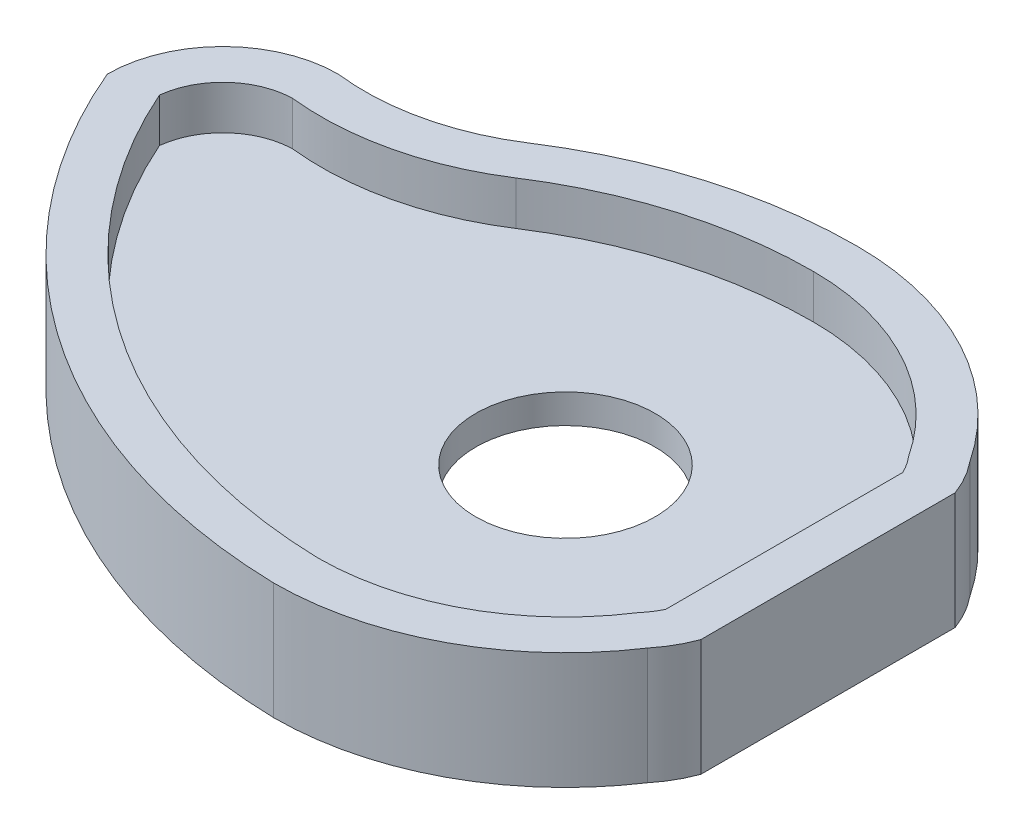
SolidWorks part; units mm, degrees
ref_plane "Front Plane" through (0, 0, 0) normal (0, 0, 1) x (1, 0, 0)
ref_plane "Top Plane" through (0, 0, 0) normal (0, 1, 0) x (1, 0, 0)
ref_plane "Right Plane" through (0, 0, 0) normal (1, 0, 0) x (0, 0, -1)
sketch "Sketch1" plane through (0, 0, 0) normal (0, 1, 0) x (1, 0, 0)
  line L0 (114.3, 55.358) -> (114.3, -55.358)
  line L1 (95.25, 55.358) -> (95.25, -55.358) construction
  line L2 (95.25, -42.12) -> (95.25, 42.12)
  line L3 (95.25, 55.358) -> (95.25, -55.358) construction
  line L4 (0, -176.5339) -> (0, 176.5339) construction
  line L5 (-247.6259, -76.2) -> (269.2373, -76.2) construction
  line L6 (-177.8, 121.45) -> (-177.8, -227.9149) construction
  line L7 (-228.08, 28.63) -> (28.179, 28.63) construction
  line L8 (69.3, 64.8307) -> (69.3, -55.358) construction
  line L9 (95.25, 42.12) -> (69.3, 42.12) construction
  line L10 (114.3, 55.358) -> (114.3, -55.358) construction
  line L11 (0, 0) -> (328.2189, 0) construction
  line L12 (95.25, 51.5873) -> (95.25, -51.5873)
  arc A0 (105.8333, 70.2019) -> (0, 127) centre (0, 0) ccw
  arc A4 (114.3, 55.358) -> (105.8333, 70.2019) centre (66.5687, 37.9695) ccw
  arc A5 (0, -127) -> (105.8333, -70.2019) centre (0, 0) ccw
  arc A6 (114.3, -55.358) -> (105.8333, -70.2019) centre (66.5687, -37.9695) cw
  arc A7 (0, 127) -> (-110.3264, 94.441) centre (0, -76.2) ccw
  arc A8 (-228.08, 28.63) -> (-177.8, 78.91) centre (-177.8, 28.63) cw
  arc A9 (-177.8, 78.91) -> (-110.3264, 94.441) centre (-165.4895, 179.7614) ccw
  arc A10 (-228.08, 28.63) -> (0, -127) centre (6.1291, 126.926) ccw
  arc A11 (0, 107.95) -> (-99.9833, 78.4434) centre (0, -76.2) ccw
  arc A12 (-178.7725, 59.8449) -> (-99.9833, 78.4434) centre (-165.4895, 179.7614) ccw
  arc A13 (-208.8363, 32.103) -> (-178.7725, 59.8449) centre (-177.8, 28.63) cw
  arc A14 (-208.8363, 32.103) -> (0.225, -107.9498) centre (6.1291, 126.926) ccw
  arc A15 (0.225, -107.9498) -> (90.5313, -58.7987) centre (0, 0) ccw
  arc A16 (95.25, -51.5873) -> (90.5313, -58.7987) centre (66.5687, -37.9695) cw
  arc A17 (95.25, 51.5873) -> (90.5313, 58.7987) centre (66.5687, 37.9695) ccw
  arc A18 (90.5313, 58.7987) -> (0, 107.95) centre (0, 0) ccw
  point P10 (114.3, 0)
  point P13 (95.25, 0)
  point P19 (0, 0)
  dimension "D1" = 254
  dimension "D7" = 203.2
  dimension "D9" = 203.2
  dimension "50.28" = 50.28
  dimension "D10" = 254
  dimension "D11" = 50.8
  dimension "D3" = 114.3
  dimension "D4" = 19.05
  dimension "D5" = 84.24
  dimension "D6" = 177.8
  dimension "D8" = 28.63
  dimension "D2" = 45
  dimension "D12" = 66.5687
  dimension "D13" = 105.8333
  dimension "D14" = 19.05
extrude "Boss-Extrude1" add sketch "Sketch1" along normal mid plane 12.7 contours A17 A18 A11 A12 A13 A14 A15 A16 L12 L2 region at (-36.1585, 0, -1.3174)
extrude "Boss-Extrude3" add sketch "Sketch1<4>" along normal mid plane 50.8 contours A8 A10 A5 A6 L0 A4 A0 A7 A9 A18 A17 L12 L2 A16 A15 A14 A13 A12 A11 region at (110.0369, 0, 0)
sketch "Sketch1<4>" plane through (0, 0, 0) normal (0, 1, 0) x (1, 0, 0) same geometry as "Sketch1"
sketch "Sketch2" plane through (0, 6.35, 0) normal (0, 1, 0) x (1, 0, 0)
  circle A0 centre (0, 0) radius 39.05
  dimension "D1" = 78.1
extrude "Cut-Extrude1" cut sketch "Sketch2" against normal through all both and the other way through all contours A0
